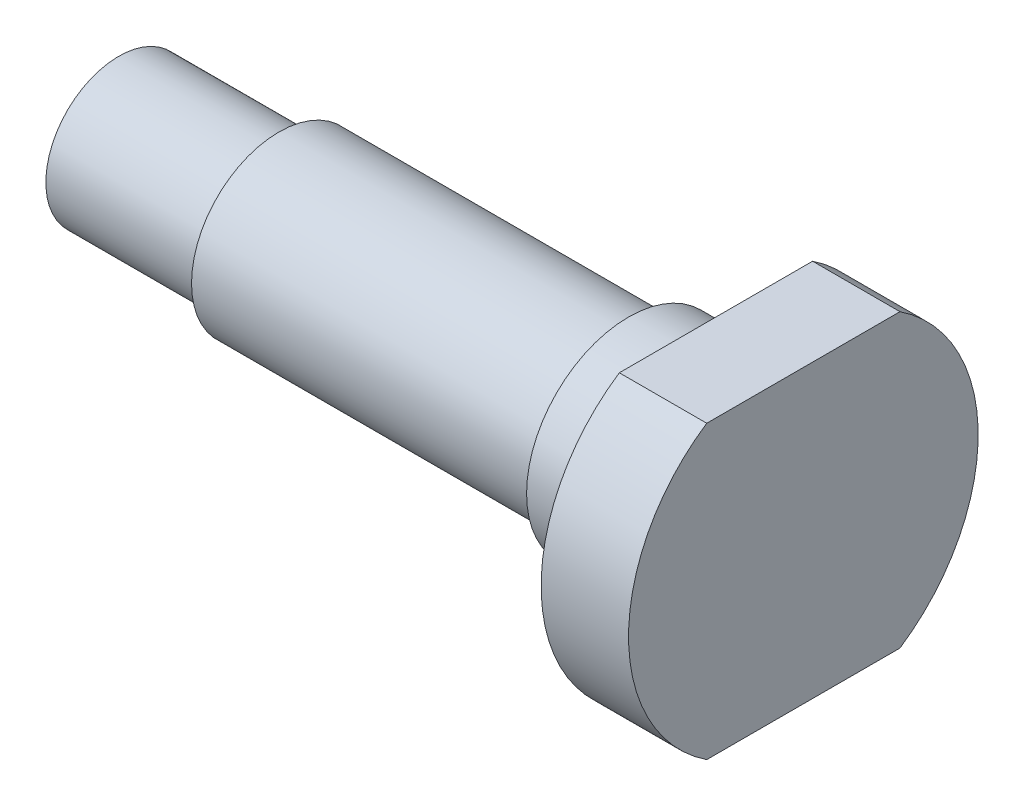
SolidWorks part; units mm, degrees
material "201 Annealed Stainless Steel (SS)"
ref_plane "Front Plane" through (0, 0, 0) normal (0, 0, 1) x (1, 0, 0)
ref_plane "Top Plane" through (0, 0, 0) normal (0, 1, 0) x (1, 0, 0)
ref_plane "Right Plane" through (0, 0, 0) normal (1, 0, 0) x (0, 0, -1)
sketch "Sketch2" plane through (0, 0, 0) normal (1, 0, 0) x (0, 0, -1)
  line L0 (-3.3166, 5) -> (3.3166, 5)
  line L1 (0, 0) -> (-50000, 0) construction
  line L2 (-3.3166, -5) -> (3.3166, -5)
  arc A0 (-3.3166, 5) -> (-3.3166, -5) centre (0, 0) ccw
  circle A1 centre (0, 0) radius 3
  circle A2 centre (0, 0) radius 2.5
  arc A3 (3.3166, -5) -> (3.3166, 5) centre (0, 0) ccw
  circle A4 centre (0, 0) radius 3.5
  dimension "D1" = 12
  dimension "D2" = 6
  dimension "D3" = 5
  dimension "D5" = 7
  dimension "D4" = 10
extrude "Boss-Extrude1" add sketch "Sketch2" along normal blind 3 contours L1 A3 L0 A0 A1 | A3 L1 A1 A0 L2 | A4 L1 A1 | L1 A4 A1 | L1 A1 A2 | A1 L1 A2 | A2 L1 | L1 A2 region at (0, 2.4293, 0) region at (0, 2.9151, 0) region at (0, 3.401, 0) region at (0, 4.8438, 0)
extrude "Boss-Extrude2" add sketch "Sketch2<4>" against normal blind 15 contours L1 A1 A2 | A1 L1 A2 region at (0, 2.9151, 0)
sketch "Sketch2<4>" plane through (0, 0, 0) normal (1, 0, 0) x (0, 0, -1) same geometry as "Sketch2"
extrude "Boss-Extrude3" add sketch "Sketch2<5>" against normal blind 20.5 contours A2 L1 | L1 A2 region at (0, 2.4293, 0)
sketch "Sketch2<5>" plane through (0, 0, 0) normal (1, 0, 0) x (0, 0, -1) same geometry as "Sketch2"
cosmetic thread "Cosmetic Thread1" parameters "D2"=3.22
extrude "Boss-Extrude4" add sketch "Sketch2<6>" against normal blind 3 contours L1 A4 A1 | A4 L1 A1 region at (0, 3.401, 0)
sketch "Sketch2<6>" plane through (0, 0, 0) normal (1, 0, 0) x (0, 0, -1) same geometry as "Sketch2"
